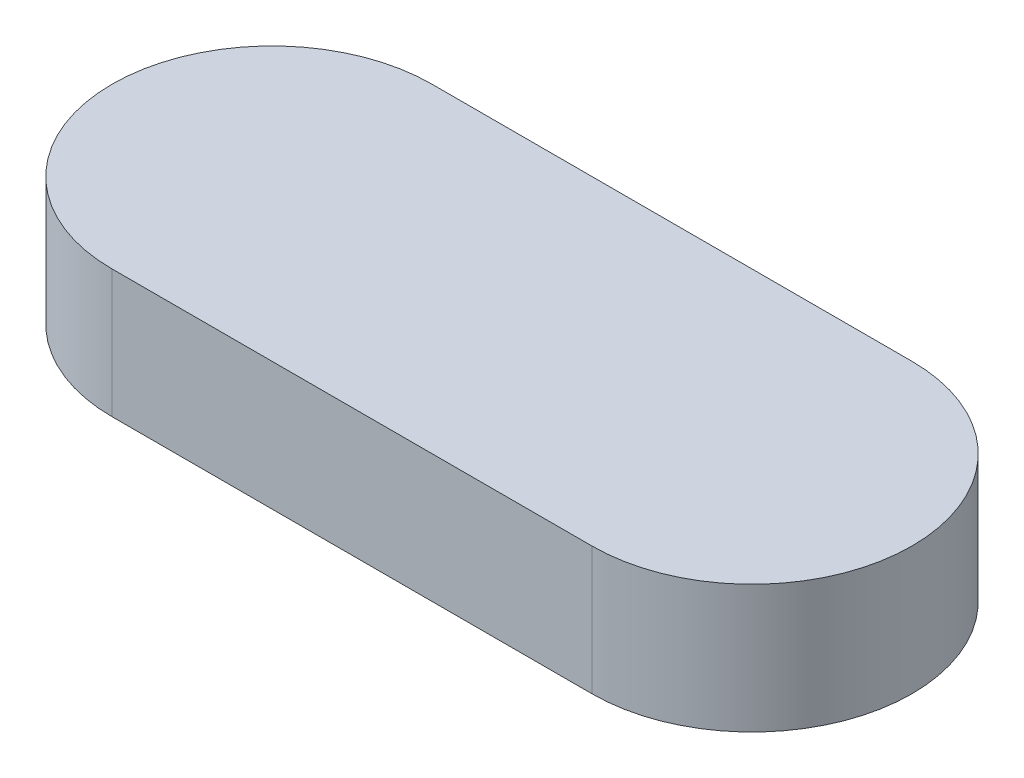
SolidWorks part; units mm, degrees
ref_plane "Front Plane" through (0, 0, 0) normal (0, 0, 1) x (1, 0, 0)
ref_plane "Top Plane" through (0, 0, 0) normal (0, 1, 0) x (1, 0, 0)
ref_plane "Right Plane" through (0, 0, 0) normal (1, 0, 0) x (0, 0, -1)
sketch "Sketch2" plane through (0, 0, 0) normal (0, 1, 0) x (1, 0, 0)
  line L1 (-15, -10) -> (15, -10)
  line L2 (-15, -10) -> (-15, 10) construction
  line L3 (-15, 10) -> (15, 10)
  line L4 (15, -10) -> (15, 10) construction
  line L5 (-15, -10) -> (15, 10) construction
  line L6 (-15, 10) -> (15, -10) construction
  arc A0 (15, 10) -> (15, -10) centre (15, 0) cw
  arc A1 (-15, 10) -> (-15, -10) centre (-15, 0) ccw
  point P0 (0, 0)
  dimension "D1" = 30
  dimension "D2" = 20
extrude "Boss-Extrude1" add sketch "Sketch2" along normal blind 8
sketch "Sketch3" plane through (0, 0, 0) normal (0, -1, 0) x (1, 0, 0)
  line L0 (-25, 0) -> (25, 0) construction
  line L1 (-15, 10) -> (-15, -10) construction
  line L2 (15, 10) -> (15, -10) construction
  line L3 (-5, 0) -> (5, 0) construction
  line L4 (-5, 5) -> (5, 5)
  line L5 (-5, -5) -> (5, -5)
  arc A0 (-15, 10) -> (-15, -10) centre (-15, 0) ccw construction
  arc A1 (15, -10) -> (15, 10) centre (15, 0) ccw construction
  arc A2 (-5, 5) -> (-5, -5) centre (-5, 0) ccw
  arc A3 (5, -5) -> (5, 5) centre (5, 0) ccw
  point P16 (-5, 0)
  point P17 (5, 0)
  point P21 (0, 0)
  dimension "D1" = 5
  dimension "D2" = 5
  dimension "D3" = 5
extrude "Cut-Extrude1" cut sketch "Sketch3" against normal blind 1
sketch "Sketch4" plane through (0, 1, 0) normal (0, -1, 0) x (1, 0, 0)
  line L1 (-8, -3.5) -> (8, -3.5)
  line L2 (-8, -3.5) -> (-8, 3.5)
  line L3 (-8, 3.5) -> (8, 3.5)
  line L4 (8, -3.5) -> (8, 3.5)
  line L5 (-8, -3.5) -> (8, 3.5) construction
  line L6 (-8, 3.5) -> (8, -3.5) construction
  point P0 (0, 0)
  dimension "D1" = 16
  dimension "D2" = 7
extrude "Cut-Extrude2" cut sketch "Sketch4" against normal blind 1
shell "Shell3" thickness 0.5 removed face at (0, 2, 0) removed face at (0, 4, -10)
sketch "Sketch5" plane through (0, 8, 0) normal (0, 1, 0) x (1, 0, 0)
  circle A0 centre (0, 0) radius 10
  dimension "D1" = 20
sketch "Sketch6" plane through (0, 8, 0) normal (0, 1, 0) x (1, 0, 0)
  line L0 (-25, 0) -> (25, 0) construction
  arc A0 (-15, 10) -> (-15, -10) centre (-15, 0) ccw construction
  arc A1 (15, -10) -> (15, 10) centre (15, 0) ccw construction
